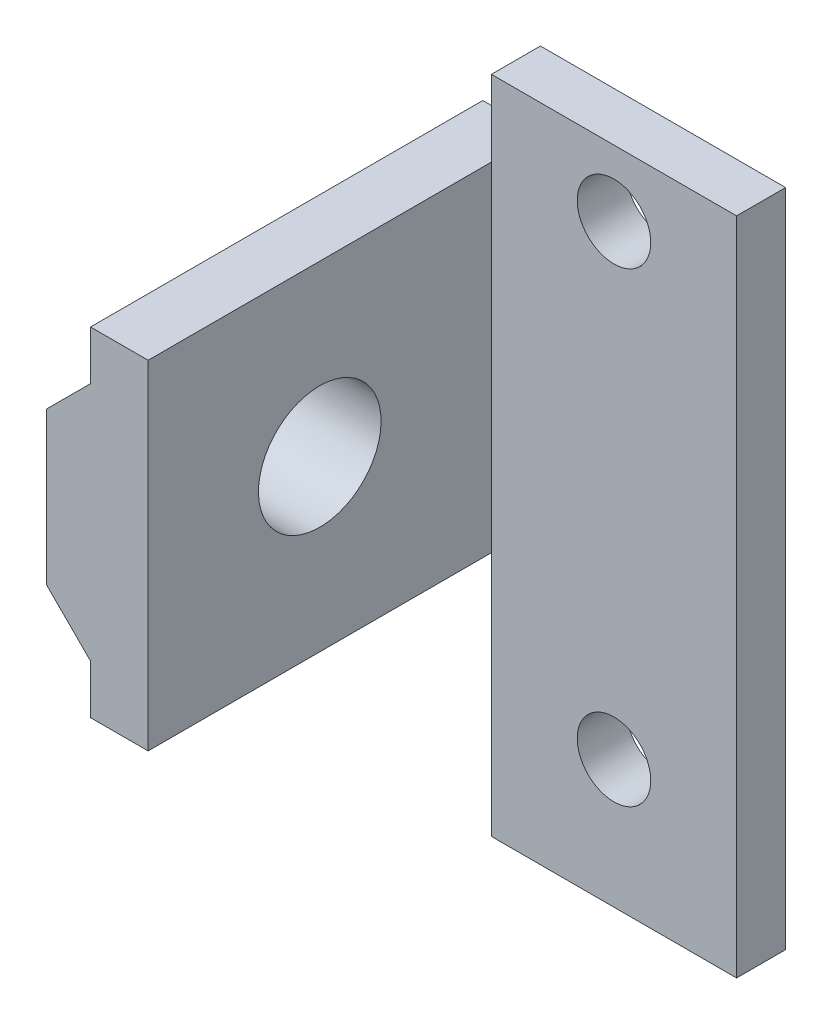
SolidWorks part; units mm, degrees
ref_plane "Front Plane" through (0, 0, 0) normal (0, 0, 1) x (1, 0, 0)
ref_plane "Top Plane" through (0, 0, 0) normal (0, 1, 0) x (1, 0, 0)
ref_plane "Right Plane" through (0, 0, 0) normal (1, 0, 0) x (0, 0, -1)
sketch "Sketch1" plane through (0, 0, 0) normal (0, 0, 1) x (1, 0, 0)
  line L0 (5, 24.22) -> (5, 5.22) construction
  line L1 (0, 0) -> (10, 0)
  line L2 (0, 0) -> (0, 26.92)
  line L3 (0, 26.92) -> (10, 26.92)
  line L4 (10, 0) -> (10, 26.92)
  circle A0 centre (5, 24.22) radius 1.5
  circle A1 centre (5, 5.22) radius 1.5
  dimension "D5" = 3
  dimension "D1" = 10
  dimension "D2" = 26.92
  dimension "D3" = 2.7
  dimension "D4" = 19
  dimension "D6" = 5
extrude "Boss-Extrude1" add sketch "Sketch1" along normal blind 2
sketch "Sketch2" plane through (0, 0, 0) normal (0, 0, -1) x (-1, 0, 0)
  line L0 (-10, 26.92) -> (0, 26.92) construction
  line L1 (0, 26.92) -> (0, 0) construction
  line L2 (2.35, 21.82) -> (4.15, 20.02)
  line L3 (0, 21.82) -> (2.35, 21.82) construction
  line L7 (4.15, 20.02) -> (4.15, 13.82)
  line L8 (4.15, 13.82) -> (2.35, 12.02)
  line L9 (2.35, 12.02) -> (0, 12.02) construction
  line L10 (0, 12.02) -> (0, 21.82)
  line L12 (2.35, 21.82) -> (0, 21.82) construction
  line L13 (2.35, 21.82) -> (2.35, 23.82)
  line L14 (2.35, 23.82) -> (0, 23.82)
  line L15 (0, 21.82) -> (0, 23.82)
  line L16 (0, 12.02) -> (2.35, 12.02) construction
  line L17 (0, 12.02) -> (0, 10.02)
  line L18 (0, 10.02) -> (2.35, 10.02)
  line L19 (2.35, 12.02) -> (2.35, 10.02)
  dimension "D1" = 2.35
  dimension "D2" = 4.15
  dimension "D3" = 5.1
  dimension "D4" = 45
  dimension "D5" = 9.8
  dimension "D6" = 2.5456
  dimension "D7" = 2
  dimension "D8" = 2
extrude "Boss-Extrude2" add sketch "Sketch2" against normal blind 16
sketch "Sketch5" plane through (0, 0, 0) normal (1, 0, 0) x (0, 0, -1)
  line L0 (-9, 23.82) -> (-9, 10.02) construction
  line L1 (-16, 23.82) -> (-2, 23.82) construction
  line L2 (-16, 10.02) -> (-2, 10.02) construction
  circle A0 centre (-9, 16.92) radius 2.5
  dimension "D1" = 5
extrude "Cut-Extrude1" cut sketch "Sketch5" against normal blind 16
